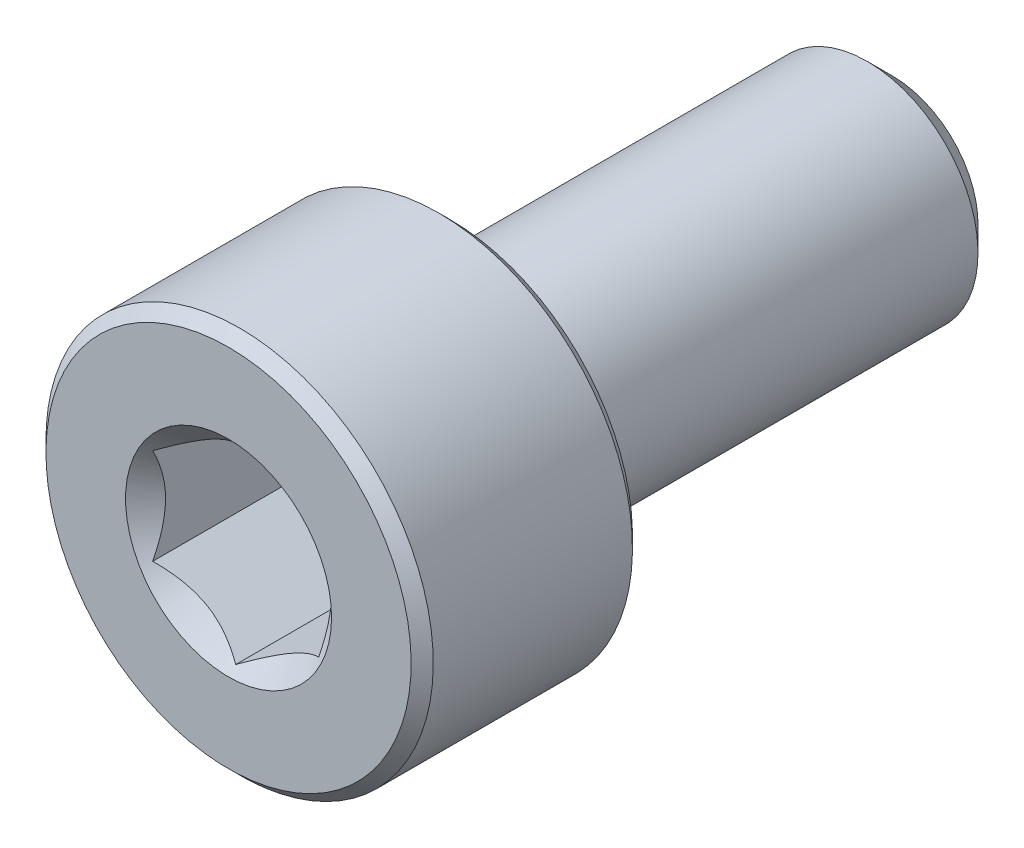
SolidWorks part; units mm, degrees
material "Alloy Steel"
ref_plane "Front Plane" through (0, 0, 0) normal (0, 0, 1) x (1, 0, 0)
ref_plane "Top Plane" through (0, 0, 0) normal (0, 1, 0) x (1, 0, 0)
ref_plane "Right Plane" through (0, 0, 0) normal (1, 0, 0) x (0, 0, -1)
sketch "Sketch1" plane through (0, 0, 0) normal (1, 0, 0) x (0, 0, -1)
  line L0 (-6, 0) -> (6, 0) construction
  line L1 (6, 0) -> (6, 1.5453) construction
  line L2 (6, 1.5453) -> (5.5453, 2) construction
  line L3 (5.5453, 2) -> (5.475, 2) construction
  line L4 (5.475, 2) -> (-2, 2) construction
  line L5 (-2, 2) -> (-2, 3.5) construction
  line L6 (-2, 3.5) -> (-6, 3.5) construction
  line L7 (-6, 3.5) -> (-6, 0) construction
  line L8 (6, 1.5453) -> (6, 2) construction
  line L9 (5.9562, 2.0758) -> (6.3062, 1.4696) construction
  line L10 (6.3062, 1.4696) -> (6.6562, 2.0758) construction
  line L11 (6.6562, 2.0758) -> (5.9562, 2.0758) construction
  line L12 (6.3062, 2.0758) -> (6.3062, 2) construction
  line L13 (6.3062, 1.4696) -> (6.3062, 1.5453) construction
  line L14 (6.2625, 1.5453) -> (6.35, 1.5453) construction
  line L15 (6, 2) -> (6.6125, 2) construction
  line L16 (5.9781, 2.0379) -> (6.6344, 2.0379) construction
  line L17 (6, 0) -> (6, -2) construction
  line L18 (-2.2, 3.5) -> (-2, 3.3) construction
  line L19 (-5.8, 3.5) -> (-6, 3.3) construction
  line L20 (-2, 2) -> (-2, 0) construction
  line L21 (-2, 1) -> (0.6667, 1) construction
  line L22 (0.6667, 1) -> (3.3333, 1) construction
  line L23 (3.3333, 1) -> (6, 1) construction
  line L24 (0.6667, 1) -> (0.6667, 2) construction
  line L25 (0.6667, 2) -> (0.6667, 3.5) construction
  line L26 (3.3333, 1) -> (3.3333, 3.5) construction
  point P0 (-6, 1.5)
  point P3 (4.25, 2)
  point P4 (0, 0)
  point P18 (3.3333, 2)
  point P22 (6.3062, 1.5453)
  point P24 (5.475, 2)
  point P25 (6.3062, 2)
  point P28 (6.3062, 2.0379)
  point P29 (4.25, -2)
  point P30 (0.6667, 2)
  point P31 (-4, 3.5)
  point P37 (-2.7, 3.5)
  point P38 (-5.7, 3.5)
  point P45 (0.6667, 1)
  point P46 (3.3333, 1)
  dimension "D2" = 0.0875
  dimension "D7" = 0.2
  dimension "D8" = 0.2
  dimension "D9" = 0.2
  dimension "D10" = 0.1
  dimension "D11" = 0.5
  dimension "Drive Size" = 3
  dimension "Head Diameter" = 7
  dimension "Head Height" = 4
  dimension "Thread Pitch" = 0.7
  dimension "Thread Dia" = 4
  dimension "Length" = 8
  dimension "D12" = 0.525
  dimension "D4" = 1.75
  dimension "D3" = 45
sketch "Sketch2" plane through (0, 0, 0) normal (1, 0, 0) x (0, 0, -1)
  line L0 (-6, 0) -> (-6, 3.3)
  line L1 (-5.8, 3.5) -> (-2.2, 3.5)
  line L2 (-2, 3.3) -> (-2, 2.2)
  line L4 (5.5453, 2) -> (6, 1.5453)
  line L5 (6, 1.5453) -> (6, 0)
  line L6 (-2, 3.5) -> (-6, 3.5) construction
  line L7 (6, 0) -> (-6, 0)
  line L8 (-5.8, 3.5) -> (-6, 3.3) construction
  line L10 (-5.8, 3.5) -> (-6, 3.3)
  line L14 (-2.2, 3.5) -> (-2, 3.3) construction
  line L16 (-2.2, 3.5) -> (-2, 3.3)
  line L17 (-2, 2) -> (-2, 3.5) construction
  line L19 (-1.8, 2) -> (5.5453, 2)
  line L20 (5.475, 2) -> (-2, 2) construction
  arc A1 (-2, 2.2) -> (-1.8, 2) centre (-1.8, 2.2) ccw
  dimension "D3" = 0.2
revolve "Revolve1" add sketch "Sketch2" angle 360 about L7
sketch "Sketch3" plane through (0, 0, 6) normal (0, 0, 1) x (1, 0, 0)
  line L1 (1.5, -0.866) -> (1.5, 0.866)
  line L2 (1.5, 0.866) -> (0, 1.7321)
  line L3 (0, 1.7321) -> (-1.5, 0.866)
  line L4 (-1.5, 0.866) -> (-1.5, -0.866)
  line L5 (-1.5, -0.866) -> (0, -1.7321)
  line L6 (0, -1.7321) -> (1.5, -0.866)
  circle A0 centre (0, 0) radius 1.5 construction
  circle A1 centre (0, 0) radius 3.5 construction
  circle A2 centre (0, 0) radius 3.5 construction
  circle A3 centre (0, 0) radius 1.7321 construction
  point P13 (0, 0)
  dimension "D1" = 3.4641
extrude "Cut-Extrude1" cut sketch "Sketch3" against normal offset from surface (3 mm away) 1 up to face at (0, 3.3, 2)
sketch "Sketch4" plane through (0, 0, 6) normal (0, 0, 1) x (1, 0, 0)
  circle A0 centre (0, 0) radius 1.862
  dimension "D1" = 3.7239
extrude "Cut-Extrude2" cut sketch "Sketch4" against normal up to vertex (2 mm away) draft 45 up to point (0, 3.5, 4)
sketch "Sketch11" plane through (0, 0, 0) normal (1, 0, 0) x (0, 0, -1)
  line L0 (-6, 0) -> (6, 0) construction
  line L1 (-6, 0) -> (6, 0) construction
  line L2 (-0.5, 0) -> (-0.5, 2) construction
  line L3 (5.475, 2) -> (-2, 2) construction
  line L4 (4.5, 0) -> (4.5, 2) construction
  line L6 (6, 1.5453) -> (6, 2) construction
  point P2 (-0.5, 0)
  point P3 (4.5, 0)
  dimension "D1" = 1.5
  dimension "D2" = 1.5
sketch "Sketch6" [suppressed] plane through (0, 0, -6) normal (0, 0, -1) x (-1, 0, 0)
  circle A0 centre (0, 0) radius 2
curve "Helix/Spiral1" [suppressed] pitch 0.7 height 8.7 turns 12.4286
sketch "Sketch10" [suppressed] plane through (0, 0, 0) normal (1, 0, 0) x (0, 0, -1)
  line L0 (-1.8, -3.5) -> (-1.8, 3.5)
  line L5 (-6, 0) -> (6, 0) construction
  line L6 (-1.8, 2) -> (-1.8, -2) construction
  point P3 (-1.8, 0)
split "Split1" [suppressed] bodies to split 106
sketch "Sketch7" [suppressed] plane through (0, 0, 0) normal (1, 0, 0) x (0, 0, -1)
  line L0 (5.9781, 2.0379) -> (6.6344, 2.0379)
  line L1 (6.6344, 2.0379) -> (6.35, 1.5453)
  line L2 (6.35, 1.5453) -> (6.2625, 1.5453)
  line L3 (6.2625, 1.5453) -> (5.9781, 2.0379)
sweep "Cut-Sweep1" [suppressed] cut profiles "Sketch7" path "Helix/Spiral1"
sketch "Sketch8" [suppressed] plane through (0, 0, 0) normal (1, 0, 0) x (0, 0, -1)
  line L0 (-2, 0) -> (-2, 2)
  line L1 (-1.8, -2) -> (-1.8, 2) construction
  line L2 (-2, 2) -> (-1.8, 2)
  line L4 (-1.8, 2) -> (-0.6453, 0)
  line L5 (-0.6453, 0) -> (-2, 0)
  line L6 (5.475, 2) -> (-2, 2) construction
  line L7 (-6, 0) -> (6, 0) construction
  dimension "D1" = 60
revolve "Revolve2" [suppressed] add sketch "Sketch8" angle 360 about L5
equation "\"D2@Sketch1\" = \"Thread Pitch@Sketch1\" / 8"
equation "\"D4@Helix/Spiral1\" = \"Thread Pitch@Sketch1\""
equation "\"D7@Sketch1\" = \"Head Height@Sketch1\" * .05"
equation "\"D8@Sketch1\"=\"D7@Sketch1\""
equation "\"D9@Sketch1\"=\"D7@Sketch1\""
equation "\"D10@Sketch1\"=\"D7@Sketch1\"/2"
equation "\"D11@Sketch1\"=\"D10@Sketch1\"*5"
equation "\"D4@Sketch1\"=\"Thread Pitch@Sketch1\"*2.5"
equation "\"D12@Sketch1\"=\"Thread Pitch@Sketch1\"*.75"
equation "\"D3@Helix/Spiral1\"=\"Length@Sketch1\"+\"Thread Pitch@Sketch1\""
equation "\"D3@Sketch2\"=\"Thread Dia@Sketch1\"*0.05"
equation "\"D1@Sketch11\"=\"Length@Sketch1\"*0.1875"
equation "\"D2@Sketch11\"=\"D1@Sketch11\""
equation "\"D1@Sketch4\"=\"D1@Sketch3\"*1.075"
